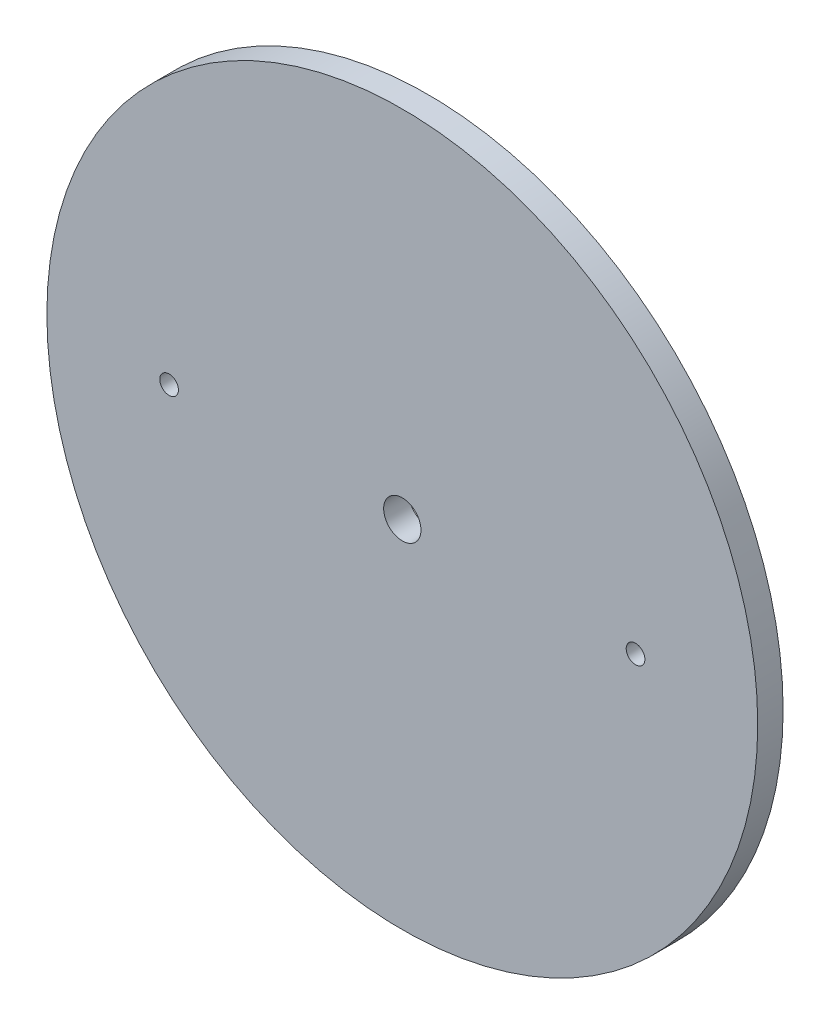
SolidWorks part; units mm, degrees
material "1060 Alloy"
ref_plane "Front Plane" through (0, 0, 0) normal (0, 0, 1) x (1, 0, 0)
ref_plane "Top Plane" through (0, 0, 0) normal (0, 1, 0) x (1, 0, 0)
ref_plane "Right Plane" through (0, 0, 0) normal (1, 0, 0) x (0, 0, -1)
ref_plane "Plane1" through (0, 0, -5) normal (0, 0, -1) x (-1, 0, 0)
sketch "Sketch1" plane through (0, 0, -5) normal (0, 0, -1) x (-1, 0, 0)
  circle A0 centre (45.9318, 0) radius 1.8373
  circle A1 centre (-45.9318, 0) radius 1.8373
  circle A2 centre (0, 0) radius 3.6745
  circle A3 centre (0, 0) radius 70
  dimension "D1" = 140
extrude "Boss-Extrude1" add sketch "Sketch1" against normal blind 5
